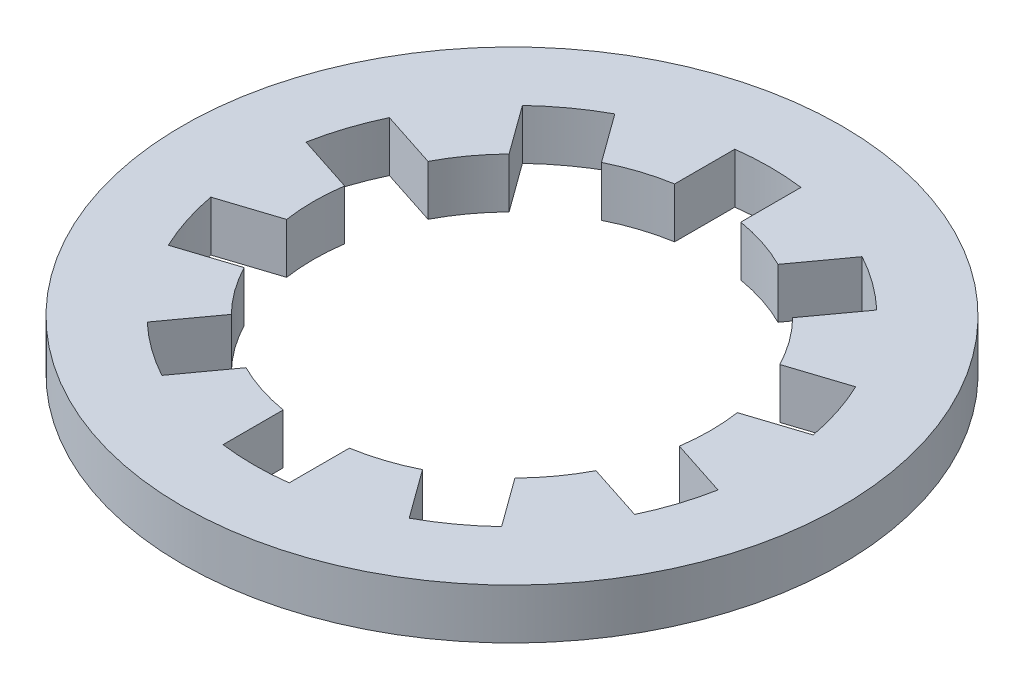
SolidWorks part; units mm, degrees
ref_plane "Front Plane" through (0, 0, 0) normal (0, 0, 1) x (1, 0, 0)
ref_plane "Top Plane" through (0, 0, 0) normal (0, 1, 0) x (1, 0, 0)
ref_plane "Right Plane" through (0, 0, 0) normal (1, 0, 0) x (0, 0, -1)
sketch "Sketch1" plane through (0, 0, 0) normal (0, 1, 0) x (1, 0, 0)
  line L0 (0, 0) -> (0, 7.5854) construction
  circle A0 centre (0, 0) radius 11.176
  circle A1 centre (0, 0) radius 6.731
  dimension "B" = 22.352
  dimension "A" = 13.462
extrude "Extrude1" add sketch "Sketch1" along normal blind 1.7018
sketch "Sketch2" plane through (0, 1.7018, 0) normal (0, 1, 0) x (-1, 0, 0)
  line L0 (0, 0) -> (0, 0.5002) construction
  line L1 (0, 0) -> (0, 9.2629) construction
  line L4 (-1.1218, 8.6781) -> (-1.1218, 6.6369)
  line L6 (1.1218, 8.6781) -> (1.1218, 6.6369)
  circle A0 centre (0, 0) radius 6.731 construction
  arc A1 (1.1218, 6.6369) -> (-1.1218, 6.6369) centre (0, 0) ccw
  arc A2 (1.1218, 8.6781) -> (-1.1218, 8.6781) centre (0, 0) ccw
  dimension "D1" = 17.5006
extrude "Cut-Extrude1" cut sketch "Sketch2" against normal through all
ref_axis "Axis1" through (0, 10.4315, 0) along (0, -1, 0)
pattern_circular "CirPattern1" count 10 over 360 about axis through (0, 10.4315, 0) along (0, -1, 0) of "Cut-Extrude1"
pattern_circular "CirPattern2" [suppressed] count 9 over 360 about axis through (0, 10.4315, 0) along (0, -1, 0) of bodies 102
equation "\"D1@Sketch2\" = \"A@Sketch1\" * 1.3"
equation "\"D2@Sketch2\" = \"A@Sketch1\" / 6"
